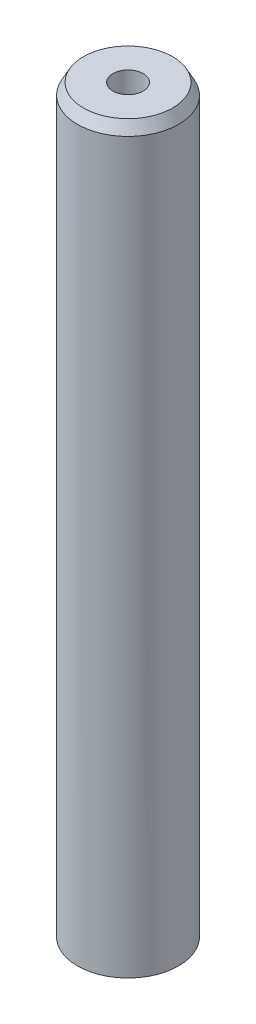
SolidWorks part; units mm, degrees
ref_plane "Front Plane" through (0, 0, 0) normal (0, 0, 1) x (1, 0, 0)
ref_plane "Top Plane" through (0, 0, 0) normal (0, 1, 0) x (1, 0, 0)
ref_plane "Right Plane" through (0, 0, 0) normal (1, 0, 0) x (0, 0, -1)
sketch "Sketch1" plane through (0, 0, 0) normal (0, 1, 0) x (1, 0, 0)
  circle A0 centre (0, 0) radius 5
  dimension "SHAFT_OD" = 10
extrude "Boss-Extrude1" add sketch "Sketch1" along normal blind 73.7593
sketch "Sketch2" plane through (0, 0, 0) normal (0, 1, 0) x (1, 0, 0)
  circle A0 centre (0, 0) radius 1.4988
  dimension "BORE_D" = 2.9976
extrude "Cut-Extrude1" cut sketch "Sketch2" along normal through all
chamfer "Chamfer1" distance 1.0997 angle 28.461 2 edges at (0, 73.7593, 5) (0, 0, 5) first distance on face at (0, 73.7593, 5) first distance on face at (0, 0, 1.4988)
